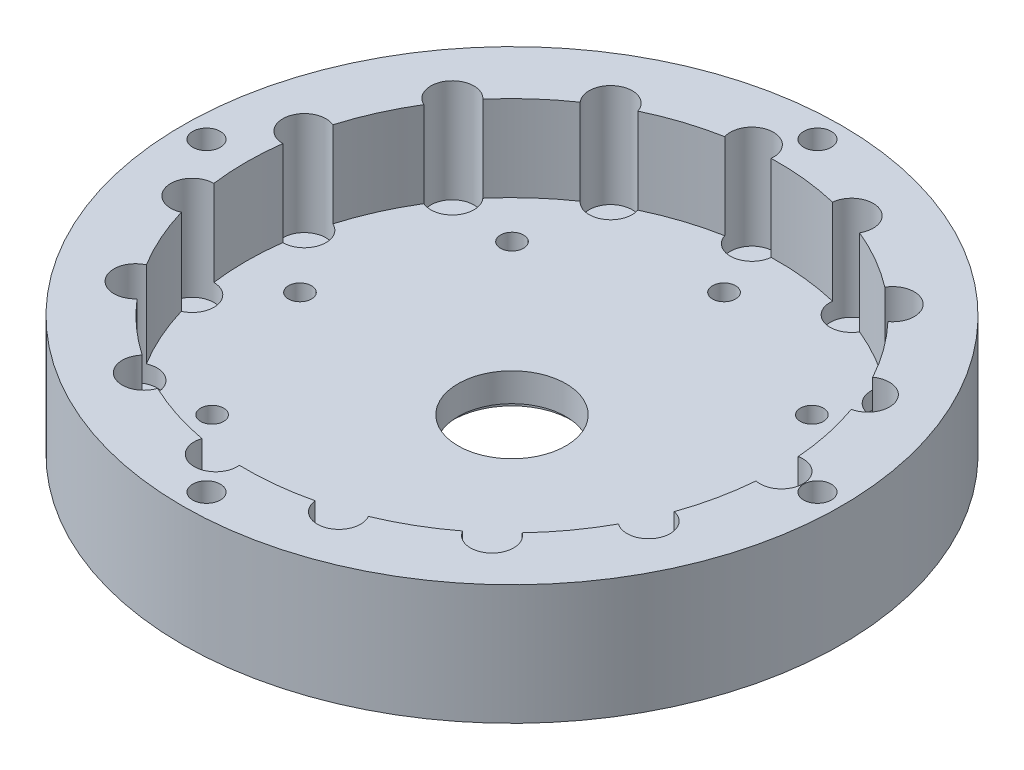
SolidWorks part; units mm, degrees
ref_plane "Front Plane" through (0, 0, 0) normal (0, 0, 1) x (1, 0, 0)
ref_plane "Top Plane" through (0, 0, 0) normal (0, 1, 0) x (1, 0, 0)
ref_plane "Right Plane" through (0, 0, 0) normal (1, 0, 0) x (0, 0, -1)
sketch "Sketch1" plane through (0, 0, 0) normal (0, 1, 0) x (1, 0, 0)
  line L0 (0, 0) -> (-42.5, 0) construction
  circle A0 centre (0, 0) radius 7.5
  circle A1 centre (0, 0) radius 45.85
  circle A2 centre (0, 0) radius 37.5 construction
  circle A3 centre (37.5, 0) radius 3
  circle A4 centre (34.258, 15.2526) radius 3
  circle A5 centre (25.0924, 27.8679) radius 3
  circle A6 centre (11.5881, 35.6646) radius 3
  circle A7 centre (-3.9198, 37.2946) radius 3
  circle A8 centre (-18.75, 32.476) radius 3
  circle A9 centre (-30.3381, 22.0419) radius 3
  circle A10 centre (-36.6805, 7.7967) radius 3
  circle A11 centre (-36.6805, -7.7967) radius 3
  circle A12 centre (-30.3381, -22.0419) radius 3
  circle A13 centre (-18.75, -32.476) radius 3
  circle A14 centre (-3.9198, -37.2946) radius 3
  circle A15 centre (11.5881, -35.6646) radius 3
  circle A16 centre (25.0924, -27.8679) radius 3
  circle A17 centre (34.258, -15.2526) radius 3
  circle A19 centre (0, 0) radius 29.5 construction
  circle A20 centre (29.5, 0) radius 1.607
  circle A21 centre (20.8597, -20.8597) radius 1.607
  circle A22 centre (0, -29.5) radius 1.607
  circle A23 centre (-20.8597, -20.8597) radius 1.607
  circle A24 centre (-29.5, 0) radius 1.607
  circle A25 centre (-20.8597, 20.8597) radius 1.607
  circle A26 centre (0, 29.5) radius 1.607
  circle A27 centre (20.8597, 20.8597) radius 1.607
  arc A28 (36.8833, 2.9359) -> (34.8888, 12.3197) centre (0, 0) ccw
  arc A29 (34.8888, -12.3197) -> (36.8833, -2.9359) centre (0, 0) ccw
  arc A30 (26.8616, -25.4451) -> (32.5004, -17.6839) centre (0, 0) ccw
  arc A31 (14.1898, -34.1709) -> (22.4979, -29.3742) centre (0, 0) ccw
  arc A32 (-0.9355, -36.9882) -> (8.6053, -35.9854) centre (0, 0) ccw
  arc A33 (-15.8991, -33.4099) -> (-6.7752, -36.3744) centre (0, 0) ccw
  arc A34 (-28.1135, -24.0547) -> (-20.9843, -30.4739) centre (0, 0) ccw
  arc A35 (-35.4669, -10.5403) -> (-31.5649, -19.3043) centre (0, 0) ccw
  arc A36 (-36.6878, 4.7967) -> (-36.6878, -4.7967) centre (0, 0) ccw
  arc A37 (-31.5649, 19.3043) -> (-35.4669, 10.5403) centre (0, 0) ccw
  arc A38 (-20.9843, 30.4739) -> (-28.1135, 24.0547) centre (0, 0) ccw
  arc A39 (-6.7752, 36.3744) -> (-15.8991, 33.4099) centre (0, 0) ccw
  arc A40 (8.6053, 35.9854) -> (-0.9355, 36.9882) centre (0, 0) ccw
  arc A41 (22.4979, 29.3742) -> (14.1898, 34.1709) centre (0, 0) ccw
  arc A42 (32.5004, 17.6839) -> (26.8616, 25.4451) centre (0, 0) ccw
  circle A43 centre (-42.5, 0) radius 1.5635
  circle A44 centre (0, 42.5) radius 1.5635
  circle A45 centre (42.5, 0) radius 1.5635
  circle A46 centre (0, 0) radius 8.25
  circle A47 centre (0, -42.5) radius 1.5635
  point P38 (0, 0)
  point P57 (0, 0)
  point P87 (0, 0)
  point P92 (0, 0)
  dimension "D2" = 15
  dimension "D3" = 75
  dimension "D4" = 91.7
  dimension "D5" = 6
  dimension "D8" = 3.214
  dimension "D9" = 59
  dimension "D6" = 37
  dimension "D12" = 3.127
  dimension "D14" = 16.5
  dimension "D11" = 42.5
  dimension "D1" = 15
  dimension "D7" = 8
  dimension "D10" = 15
  dimension "D13" = 4
extrude "Boss-Extrude1" add sketch "Sketch1" against normal blind 4.7625 contours A4 A42 A5 A41 A6 A40 A7 A39 A8 A38 A9 A37 A10 A36 A11 A35 A12 A34 A13 A33 A14 A32 A15 A31 A16 A30 A17 A29 A3 A28 A0 A20 A21 A22 A23 A24 A25 A26 A27 | A3 | A17 | A4 | A5 | A6 | A7 | A8 | A9 | A10 | A11 | A12 | A13 | A14 | A15 | A16 | A1 A42 A4 A28 A3 A29 A17 A30 A16 A31 A15 A32 A14 A33 A13 A34 A12 A35 A11 A36 A10 A37 A9 A38 A8 A39 A7 A40 A6 A41 A5 | A22 | A23 | A24 | A25 | A26 | A27 | A20 | A21 | A46 A0 region at (-44.5532, 0, 0) region at (37.5, 0, 0) region at (33.4543, 0, 0) region at (34.258, 0, -15.2526) region at (34.258, 0, 15.2526) region at (25.0924, 0, -27.8679) region at (25.0924, 0, 27.8679) region at (11.5881, 0, -35.6646) region at (11.5881, 0, 35.6646) region at (-3.9198, 0, -37.2946) region at (-3.9198, 0, 37.2946) region at (-18.75, 0, -32.476) region at (-18.75, 0, 32.476) region at (-30.3381, 0, -22.0419) region at (-30.3381, 0, 22.0419) region at (-36.6805, 0, -7.7967) region at (-36.6805, 0, 7.7967) region at (29.5, 0, 0) region at (20.8597, 0, 20.8597) region at (0, 0, 29.5) region at (-20.8597, 0, 20.8597) region at (-29.5, 0, 0) region at (-20.8597, 0, -20.8597) region at (0, 0, -29.5) region at (20.8597, 0, -20.8597) region at (-8.0167, 0, 0)
extrude "Cut-Extrude1" cut sketch "Sketch1<6>" against normal blind 2.4105 contours A24 | A25 | A26 | A27 | A20 | A21 | A22 | A23 | A10 | A11 | A9 | A12 | A13 | A14 | A15 | A16 | A17 | A3 | A4 | A5 | A6 | A7 | A8 region at (37.5, 0, 0) region at (34.258, 0, -15.2526) region at (34.258, 0, 15.2526) region at (25.0924, 0, -27.8679) region at (25.0924, 0, 27.8679) region at (11.5881, 0, -35.6646) region at (11.5881, 0, 35.6646) region at (-3.9198, 0, -37.2946) region at (-3.9198, 0, 37.2946) region at (-18.75, 0, -32.476) region at (-18.75, 0, 32.476) region at (-30.3381, 0, -22.0419) region at (-30.3381, 0, 22.0419) region at (-36.6805, 0, -7.7967) region at (-36.6805, 0, 7.7967) region at (29.5, 0, 0) region at (20.8597, 0, 20.8597) region at (0, 0, 29.5) region at (-20.8597, 0, 20.8597) region at (-29.5, 0, 0) region at (-20.8597, 0, -20.8597) region at (0, 0, -29.5) region at (20.8597, 0, -20.8597)
sketch "Sketch1<6>" plane through (0, 0, 0) normal (0, 1, 0) x (1, 0, 0) same geometry as "Sketch1"
extrude "Boss-Extrude2" add sketch "Sketch1<7>" along normal blind 11.9355 contours A1 A42 A4 A28 A3 A29 A17 A30 A16 A31 A15 A32 A14 A33 A13 A34 A12 A35 A11 A36 A10 A37 A9 A38 A8 A39 A7 A40 A6 A41 A5 region at (-44.5532, 0, 0)
sketch "Sketch1<7>" plane through (0, 0, 0) normal (0, 1, 0) x (1, 0, 0) same geometry as "Sketch1"
sketch "Sketch2" plane through (0, 11.9355, 0) normal (0, 1, 0) x (1, 0, 0)
  circle A0 centre (-42.5, 0) radius 1.925
  circle A3 centre (0, 42.5) radius 1.925
  circle A4 centre (42.5, 0) radius 1.925
  circle A5 centre (0, -42.5) radius 1.925
  point P3 (0, -42.5)
  point P10 (0, 0)
  point P14 (0, 0)
  dimension "D2" = 3.85
  dimension "D1" = 4
extrude "Cut-Extrude2" cut sketch "Sketch2" against normal blind 4
extrude "Cut-Extrude3" cut sketch "Sketch1<8>" along normal blind 0.8 from offset 4.7625 contours A46 A0 region at (-8.0167, 0, 0) offset against normal yes
sketch "Sketch1<8>" plane through (0, 0, 0) normal (0, 1, 0) x (1, 0, 0) same geometry as "Sketch1"
equation "\"D2@Sketch1\"=\"smallBearOD\"+\"smallBearOTight\""
equation "\"D3@Sketch1\"=\"pinCircleDiam\""
equation "\"D5@Sketch1\"=\"pinDiam\""
equation "\"D8@Sketch1\"=\"ballBearDiam\""
equation "\"D1@Cut-Extrude1\"=\"ballBearDiam\"*0.75"
equation "\"D1@Boss-Extrude2\"=\"ballBearDiam\"*0.75mm+2*\"sheetThickness\""
equation "\"largeBearOD\"= 21mm"
equation "\"largeBearID\" = 15mm"
equation "\"largeBearOTight\"= 0.127mm'calibrate - hold onto gears"
equation "\"largeBearITight\"= 0mm'calibrate - hold onto eccentric nut"
equation "\"largeBearFlangeDiam\" = 22.5mm"
equation "\"largeBearFlangeWidth\" = 0.8mm"
equation "\"smallBearOD\"= 15mm"
equation "\"smallBearOTight\"= 0mm'calibrate - hold onto bottom of gearbox"
equation "\"smallBearOLoose\"= 0mm'calibrate - able to take off topHat"
equation "\"smallBearID\" = 10mm"
equation "\"smallBearITight\" = 0mm'hold onto "
equation "\"pinCircleDiam\"= 75mm"
equation "\"pinDiam\"= 6mm"
equation "\"sheetThickness\"= 0.1875in"
equation "\"ballBearDiam\"= 3.214mm"
equation "\"thrustBearingThickness\"= 5mm'measure this irl and change"
equation "\"thrustBearingID\"= 0mm'measure this irl and change"
equation "\"thrustBearingOD\"= 0mm'measure this irl and change"
equation "\"eccentricity\" = 1mm"
equation "\"D6@Sketch1\"=(\"pinCircleDiam\"-1)/2"
equation "\"D1@Boss-Extrude1\"=\"sheetThickness\""
equation "\"D19@Cut-Extrude3\"=\"sheetThickness\""
